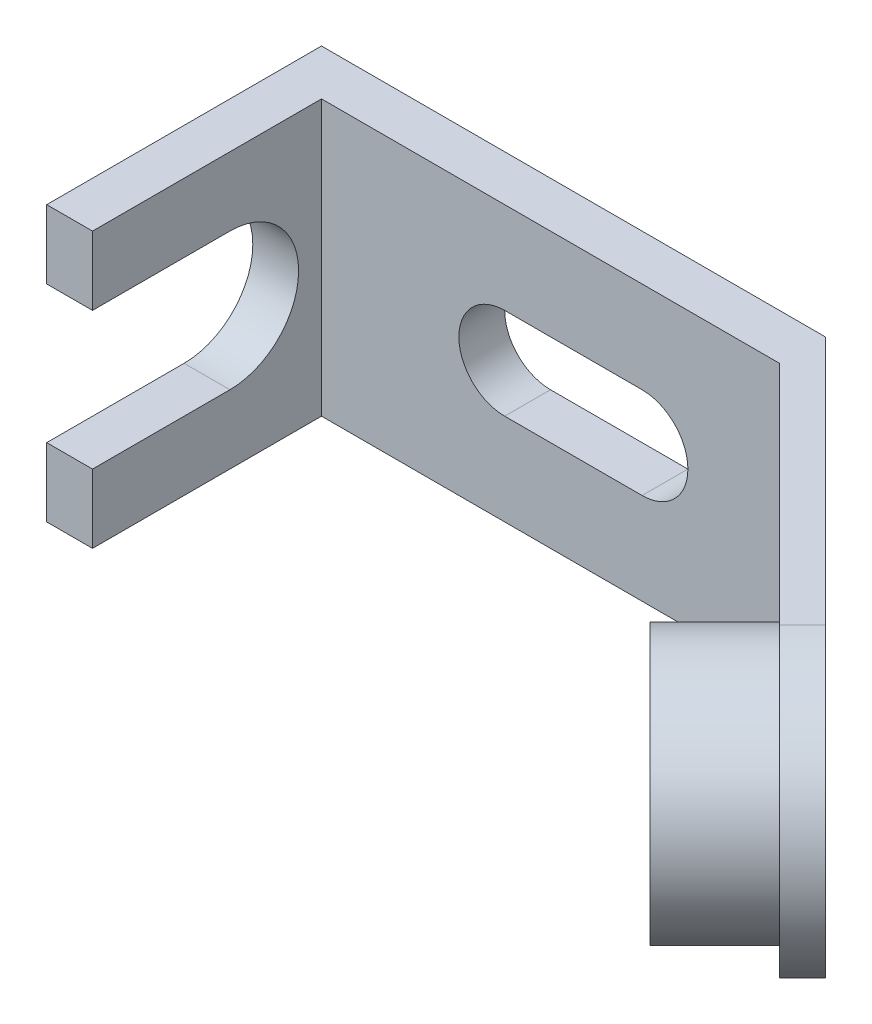
SolidWorks part; units mm, degrees
ref_plane "Front Plane" through (0, 0, 0) normal (0, 0, 1) x (1, 0, 0)
ref_plane "Top Plane" through (0, 0, 0) normal (0, 1, 0) x (1, 0, 0)
ref_plane "Right Plane" through (0, 0, 0) normal (1, 0, 0) x (0, 0, -1)
sketch "Sketch1" plane through (0, 0, 0) normal (0, 0, 1) x (1, 0, 0)
  line L0 (-10, 0) -> (20, 0) construction
  line L1 (-50, -30) -> (50, -30)
  line L2 (-50, -30) -> (-50, 30)
  line L3 (-50, 30) -> (50, 30)
  line L4 (50, -30) -> (50, 30)
  line L5 (-50, -30) -> (50, 30) construction
  line L6 (-50, 30) -> (50, -30) construction
  line L7 (-10, 10) -> (20, 10)
  line L8 (-10, -10) -> (20, -10)
  arc A0 (-10, 10) -> (-10, -10) centre (-10, 0) ccw
  arc A1 (20, -10) -> (20, 10) centre (20, 0) ccw
  point P0 (0, 0)
  point P8 (5, 0)
  dimension "D5" = 10
  dimension "D1" = 60
  dimension "D2" = 100
  dimension "D3" = 30
  dimension "D4" = 40
extrude "Boss-Extrude1" add sketch "Sketch1" along normal blind 10
sketch "Sketch3" plane through (-50, 0, 0) normal (-1, 0, 0) x (0, 0, 1)
  line L1 (10, -30) -> (0, -30) construction
  line L2 (0, 30) -> (60, 30)
  line L3 (0, 30) -> (0, -30)
  line L4 (0, -30) -> (60, -30)
  line L6 (0, 0) -> (79.3814, 0) construction
  line L7 (60, 30) -> (60, 15)
  line L8 (60, 15) -> (30, 15)
  line L9 (30, 42.6735) -> (30, -42.099) construction
  line L10 (60, -15) -> (30, -15)
  line L11 (60, -30) -> (60, -15)
  arc A0 (30, 15) -> (30, -15) centre (30, 0) ccw
  dimension "D1" = 60
  dimension "D2" = 15
  dimension "D3" = 30
extrude "Boss-Extrude2" add sketch "Sketch3" along normal blind 10
sketch "Sketch4" plane through (0, -30, 0) normal (0, -1, 0) x (1, 0, 0)
  line L0 (50, 10) -> (125, 85)
  line L1 (50, 0) -> (130, 80)
  line L2 (-60, 0) -> (50, 0) construction
  line L3 (125, 85) -> (130, 80)
  line L4 (50, 10) -> (50, 0) construction
  line L5 (50, 10) -> (50, 0)
  dimension "D1" = 45
  dimension "D2" = 80
extrude "Boss-Extrude3" add sketch "Sketch4" against normal up to surface (60 mm away) up to face at (-20, 30, 23.3333)
sketch "Sketch5" plane through (20, 0, -20) normal (-0.7071, 0, 0.7071) x (0.7071, 0, 0.7071)
  line L0 (112.4264, 40.7998) -> (112.4264, -56.6456) construction
  line L1 (42.4264, -30) -> (42.4264, 30) construction
  line L2 (42.4264, 30) -> (148.4924, 30) construction
  line L3 (148.4924, -30) -> (42.4264, -30) construction
  line L4 (148.4924, 30) -> (148.4924, -30) construction
  line L5 (148.4924, -30) -> (112.4264, -30)
  line L6 (148.4924, 30) -> (148.4924, -30)
  line L7 (112.4264, 30) -> (148.4924, 30)
  circle A0 centre (112.4264, 0) radius 15
  circle A1 centre (112.4264, 0) radius 25
  arc A2 (112.4264, 30) -> (112.4264, -30) centre (112.4264, 0) cw
  point P11 (0, 0)
  line M4 (148.4924, 30) -> (42.4264, 30)
  line M6 (42.4264, -30) -> (148.4924, -30)
  line M7 (148.4924, -30) -> (148.4924, 30)
  dimension "D2" = 30
  dimension "D3" = 50
  dimension "D1" = 70
extrude "Boss-Extrude4" add sketch "Sketch5" along normal blind 20 contours L0 A1 A0 | A1 L0 A0 region at (111.718, 17.2824, 71.718) region at (99.1022, 20, 59.1022)
extrude "Cut-Extrude3" cut sketch "Sketch5<4>" against normal blind 20 contours A2 M4 M6 M7 region at (112.2487, -29.2999, 72.2487)
sketch "Sketch5<4>" plane through (20, 0, -20) normal (-0.7071, 0, 0.7071) x (0.7071, 0, 0.7071) same geometry as "Sketch5"
sketch "Sketch6" plane through (20, 0, -20) normal (-0.7071, 0, 0.7071) x (0.7071, 0, 0.7071)
  circle A1 centre (112.4264, 0) radius 15
  circle A2 centre (112.4264, 0) radius 15
  dimension "D1" = 0
extrude "Cut-Extrude4" cut sketch "Sketch6" against normal blind 20
